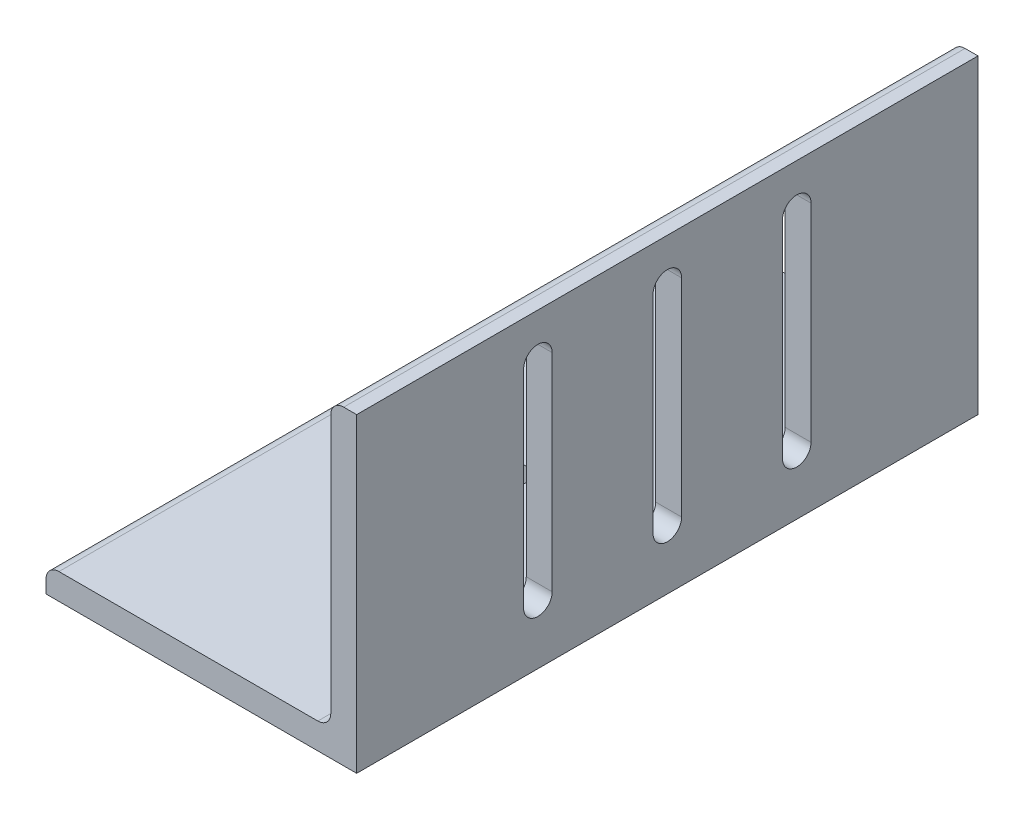
SolidWorks part; units mm, degrees
ref_plane "Front Plane" through (0, 0, 0) normal (0, 0, 1) x (1, 0, 0)
ref_plane "Top Plane" through (0, 0, 0) normal (0, 1, 0) x (1, 0, 0)
ref_plane "Right Plane" through (0, 0, 0) normal (1, 0, 0) x (0, 0, -1)
sketch "Sketch2" plane through (0, 0, 0) normal (0, 0, 1) x (1, 0, 0)
  line L0 (-38.1, 0) -> (38.1, 0)
  line L1 (38.1, 0) -> (38.1, 76.2)
  line L2 (38.1, 76.2) -> (31.75, 76.2) construction
  line L3 (31.75, 73.025) -> (31.75, 9.525)
  line L4 (28.575, 6.35) -> (-34.925, 6.35)
  line L5 (-38.1, 0) -> (-38.1, 6.35) construction
  line L6 (34.925, 76.2) -> (38.1, 76.2)
  line L7 (-38.1, 3.175) -> (-38.1, 0)
  arc A0 (31.75, 73.025) -> (34.925, 76.2) centre (34.925, 73.025) cw
  arc A1 (-38.1, 3.175) -> (-34.925, 6.35) centre (-34.925, 3.175) cw
  arc A2 (31.75, 9.525) -> (28.575, 6.35) centre (28.575, 9.525) cw
  dimension "Vert" = 76.2
  dimension "Horz" = 76.2
  dimension "Thickness" = 6.35
extrude "Boss-Extrude1" add sketch "Sketch2" along normal mid plane 152.4
ref_plane "Contact Plane 1" through (0, 6.35, 0) normal (0, 1, 0) x (1, 0, 0)
ref_plane "Contact Plane 2" through (31.75, 0, 0) normal (-1, 0, 0) x (0, 0, 1)
sketch "Sketch3" plane through (38.1, 0, 0) normal (1, 0, 0) x (0, 0, -1)
  line L0 (-31.75, 65.4) -> (-31.75, 14.6) construction
  line L1 (-28.25, 65.4) -> (-28.25, 14.6)
  line L2 (-35.25, 65.4) -> (-35.25, 14.6)
  line L3 (0, 0) -> (0, 76.2) construction
  line L4 (-76.2, 0) -> (76.2, 0) construction
  line L5 (-76.2, 76.2) -> (76.2, 76.2) construction
  line L6 (31.75, 65.4) -> (31.75, 14.6) construction
  line L7 (28.25, 65.4) -> (28.25, 14.6)
  line L8 (35.25, 65.4) -> (35.25, 14.6)
  line L9 (0, 65.4) -> (0, 14.6) construction
  line L10 (3.5, 65.4) -> (3.5, 14.6)
  line L11 (-3.5, 65.4) -> (-3.5, 14.6)
  arc A0 (-28.25, 65.4) -> (-35.25, 65.4) centre (-31.75, 65.4) ccw
  arc A1 (-35.25, 14.6) -> (-28.25, 14.6) centre (-31.75, 14.6) ccw
  arc A2 (28.25, 65.4) -> (35.25, 65.4) centre (31.75, 65.4) cw
  arc A3 (35.25, 14.6) -> (28.25, 14.6) centre (31.75, 14.6) cw
  arc A4 (3.5, 65.4) -> (-3.5, 65.4) centre (0, 65.4) ccw
  arc A5 (-3.5, 14.6) -> (3.5, 14.6) centre (0, 14.6) ccw
  point P2 (-31.75, 40)
  point P15 (31.75, 40)
  point P22 (0, 40)
  point P27 (0, 0)
  dimension "D1" = 3.5
  dimension "D3" = 31.75
  dimension "D5" = 3.5
  dimension "D2" = 50.8
  dimension "D4" = 40
  dimension "D6" = 50.8
extrude "Cut-Extrude1" cut sketch "Sketch3" against normal blind 10
sketch "Sketch4" plane through (0, 0, 0) normal (0, -1, 0) x (1, 0, 0)
  line L0 (-38.1, 76.2) -> (-38.1, -76.2) construction
  line L1 (-38.1, -76.2) -> (38.1, -76.2) construction
  circle A0 centre (0, 25.4) radius 3.5
  circle A1 centre (0, -25.4) radius 3.5
  circle A2 centre (0, 0) radius 3.5
  dimension "D1" = 7
  dimension "D2" = 7
  dimension "D3" = 38.1
  dimension "D4" = 76.2
extrude "Cut-Extrude2" cut sketch "Sketch4" against normal blind 10
